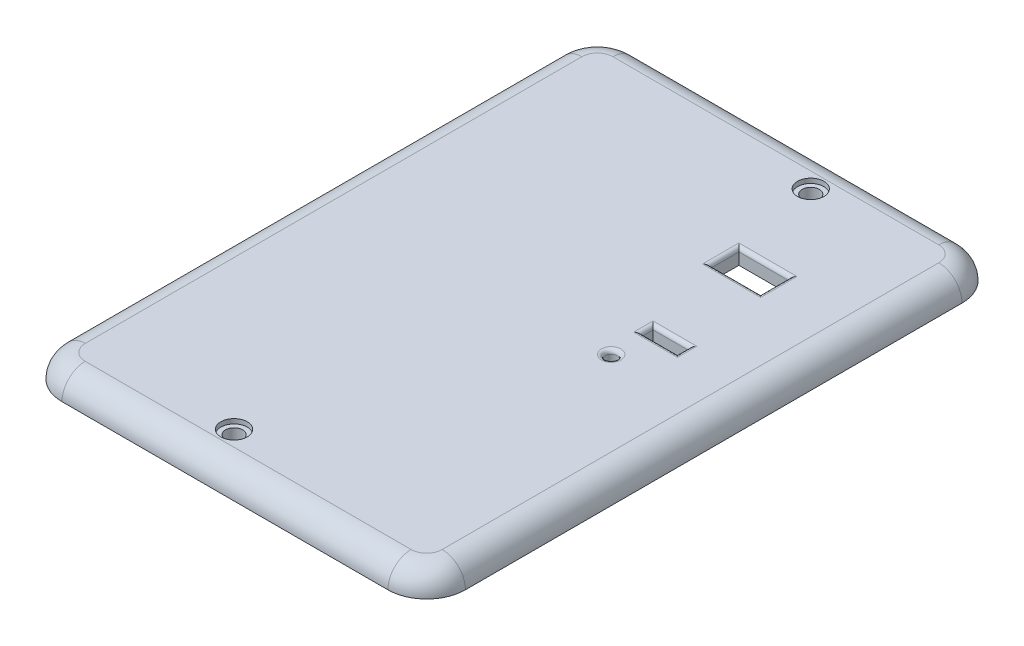
SolidWorks part; units mm, degrees
ref_plane "Front Plane" through (0, 0, 0) normal (0, 0, 1) x (1, 0, 0)
ref_plane "Top Plane" through (0, 0, 0) normal (0, 1, 0) x (1, 0, 0)
ref_plane "Right Plane" through (0, 0, 0) normal (1, 0, 0) x (0, 0, -1)
sketch "Sketch1" plane through (0, 0, 0) normal (0, 1, 0) x (1, 0, 0)
  line L1 (-19.2069, 30.931) -> (22.7931, 30.931)
  line L2 (-24.2069, 25.931) -> (-24.2069, -38.069)
  line L3 (-19.2069, -43.069) -> (22.7931, -43.069)
  line L4 (27.7931, 25.931) -> (27.7931, -38.069)
  arc A0 (22.7931, -43.069) -> (27.7931, -38.069) centre (22.7931, -38.069) ccw
  arc A1 (-24.2069, -38.069) -> (-19.2069, -43.069) centre (-19.2069, -38.069) ccw
  arc A2 (22.7931, 30.931) -> (27.7931, 25.931) centre (22.7931, 25.931) cw
  arc A3 (-19.2069, 30.931) -> (-24.2069, 25.931) centre (-19.2069, 25.931) ccw
  point P6 (27.7931, -43.069)
  point P11 (27.7931, 30.931)
  point P14 (-24.2069, 30.931)
  dimension "D3" = 5
  dimension "D1" = 52
  dimension "D2" = 74
extrude "Boss-Extrude1" add sketch "Sketch1" along normal blind 3
sketch "Sketch3" plane through (0, 0, 0) normal (0, -1, 0) x (-1, 0, 0)
  line L0 (24.2069, 25.931) -> (24.2069, -38.069) construction
  line L1 (18.2069, 29.931) -> (-21.7931, 29.931)
  line L2 (23.2069, 24.931) -> (23.2069, -37.069)
  line L3 (18.2069, -42.069) -> (-21.7931, -42.069)
  line L4 (-26.7931, 24.931) -> (-26.7931, -37.069)
  line L5 (-27.7931, -38.069) -> (-27.7931, 25.931) construction
  line L6 (19.2069, -43.069) -> (-22.7931, -43.069) construction
  line L7 (-22.7931, 30.931) -> (19.2069, 30.931) construction
  arc A0 (-21.7931, 29.931) -> (-26.7931, 24.931) centre (-21.7931, 24.931) ccw
  arc A1 (-21.7931, -42.069) -> (-26.7931, -37.069) centre (-21.7931, -37.069) cw
  arc A2 (23.2069, -37.069) -> (18.2069, -42.069) centre (18.2069, -37.069) cw
  arc A3 (18.2069, 29.931) -> (23.2069, 24.931) centre (18.2069, 24.931) cw
  dimension "D5" = 5
  dimension "D1" = 1
  dimension "D2" = 1
  dimension "D3" = 1
  dimension "D4" = 1
extrude "Cut-Extrude1" cut sketch "Sketch3" against normal blind 1
fillet "Fillet1" radius 3 8 edges at (-22.7424, 3, -29.4666) (1.7931, 3, -30.931) (26.3286, 3, -29.4666) (27.7931, 3, 6.069) (26.3286, 3, 41.6045) (1.7931, 3, 43.069) (-22.7424, 3, 41.6045) (-24.2069, 3, 6.069)
sketch "Sketch6" plane through (0, 1, 0) normal (0, -1, 0) x (1, 0, 0)
  line L0 (-23.2069, 37.069) -> (-23.2069, -24.931) construction
  line L1 (-22.6069, -4.231) -> (-10.6069, -4.231)
  line L2 (-22.6069, -4.231) -> (-22.6069, 16.269)
  line L3 (-22.6069, 16.269) -> (-10.6069, 16.269)
  line L4 (-10.6069, -4.231) -> (-10.6069, 16.269)
  line L5 (22.7931, -30.931) -> (-19.2069, -30.931) construction
  dimension "D1" = 12
  dimension "D2" = 20.5
  dimension "D3" = 0.6
  dimension "D4" = 26.7
extrude "Boss-Extrude3" add sketch "Sketch6" along normal blind 4.5
sketch "Sketch13" plane through (0, -3.5, 0) normal (0, -1, 0) x (1, 0, 0)
  line L0 (-10.6069, 16.269) -> (-22.6069, 16.269) construction
  line L1 (-15.1069, 16.269) -> (-12.1069, 16.269)
  line L2 (-15.1069, 16.269) -> (-15.1069, -4.231)
  line L3 (-15.1069, -4.231) -> (-12.1069, -4.231)
  line L4 (-12.1069, 16.269) -> (-12.1069, -4.231)
  line L5 (-22.6069, -4.231) -> (-10.6069, -4.231) construction
  line L6 (-22.6069, 16.269) -> (-22.6069, -4.231) construction
  dimension "D1" = 7.5
  dimension "D2" = 3
sketch "Sketch28" plane through (0, -3.5, 0) normal (0, -1, 0) x (1, 0, 0)
  line L0 (-22.6069, -4.231) -> (-10.6069, -4.231) construction
  line L1 (-22.6069, 16.269) -> (-22.3069, 16.269)
  line L2 (-22.6069, 16.269) -> (-22.6069, -4.231)
  line L3 (-22.6069, -4.231) -> (-22.3069, -4.231)
  line L4 (-22.3069, 16.269) -> (-22.3069, -4.231)
  dimension "D1" = 0.3
extrude "Cut-Extrude18" cut sketch "Sketch28" against normal blind 4.5
sketch "Sketch44" plane through (0, 1, 0) normal (0, -1, 0) x (1, 0, 0)
  line L0 (21.7931, 42.069) -> (-18.2069, 42.069) construction
  line L2 (26.7931, -24.931) -> (26.7931, 37.069) construction
  circle A0 centre (-2.0269, 38.069) radius 1.1
  dimension "D1" = 4
  dimension "D2" = 28.82
extrude "Cut-Extrude26" cut sketch "Sketch44" against normal blind 10
sketch "Sketch45" plane through (0, 1, 0) normal (0, -1, 0) x (1, 0, 0)
  line L0 (-18.2069, -29.931) -> (21.7931, -29.931) construction
  line L1 (26.7931, -24.931) -> (26.7931, 37.069) construction
  circle A0 centre (8.2931, -25.931) radius 1.1
  dimension "D1" = 4
  dimension "D2" = 18.5
extrude "Cut-Extrude27" cut sketch "Sketch45" against normal blind 10
sketch "Sketch47" plane through (0, 3, 0) normal (0, 1, 0) x (1, 0, 0)
  circle A0 centre (8.2931, 25.931) radius 1.7
  circle A1 centre (-2.0269, -38.069) radius 1.7
extrude "Cut-Extrude29" cut sketch "Sketch47" against normal blind 0.6
extrude "Cut-Extrude30" cut sketch "Sketch13" against normal blind 3 contours L2 L3 L4 L1
sketch "Sketch48" plane through (0, 3, 0) normal (0, 1, 0) x (1, 0, 0)
  line L0 (13.3693, 0.5278) -> (18.0165, -0.9722) construction
  line L1 (13.3693, -0.9722) -> (18.0165, -0.9722)
  line L2 (13.3693, -0.9722) -> (13.3693, 0.5278)
  line L3 (13.3693, 0.5278) -> (18.0165, 0.5278)
  line L4 (18.0165, -0.9722) -> (18.0165, 0.5278)
  line L9 (18.0165, 0.5278) -> (13.3693, -0.9722) construction
  line L10 (13.3693, -0.2222) -> (18.0165, -0.2222) construction
  circle A0 centre (13.9198, -5.4182) radius 0.75
  dimension "D1" = 0.75
sketch "Sketch49" plane through (0, 3, 0) normal (0, 1, 0) x (1, 0, 0)
  line L1 (10.2017, 14.7694) -> (16.6873, 14.7694)
  line L2 (10.2017, 14.7694) -> (10.2017, 11.0747)
  line L3 (10.2017, 11.0747) -> (16.6873, 11.0747)
  line L4 (16.6873, 14.7694) -> (16.6873, 11.0747)
extrude "Cut-Extrude31" cut sketch "Sketch49" against normal blind 8
extrude "Cut-Extrude33" cut sketch "Sketch48" against normal blind 8
fillet "Fillet2" radius 0.5 9 edges at (13.9198, 3, 6.1682) (15.6929, 3, 0.9722) (18.0165, 3, 0.2222) (13.3693, 3, 0.2222) (15.6929, 3, -0.5278) (13.4445, 3, -11.0747) (16.6873, 3, -12.922) (10.2017, 3, -12.922) (13.4445, 3, -14.7694)
sketch "Sketch51" plane through (0, 0, 0) normal (0, 1, 0) x (1, 0, 0)
  line L0 (26.7931, 24.931) -> (26.7931, -37.069) construction
  line L1 (-18.2069, 29.931) -> (21.7931, 29.931) construction
  line L2 (-23.2069, -37.069) -> (-23.2069, 24.931) construction
  line L3 (21.7931, -42.069) -> (-18.2069, -42.069) construction
  line L4 (26.7931, 24.931) -> (26.7931, -37.069)
  line L5 (-18.2069, 29.931) -> (21.7931, 29.931)
  line L6 (-23.2069, -37.069) -> (-23.2069, 24.931)
  line L7 (21.7931, -42.069) -> (-18.2069, -42.069)
  line L8 (21.7931, -41.569) -> (-18.2069, -41.569)
  line L9 (-22.7069, -37.069) -> (-22.7069, 24.931)
  line L10 (-18.2069, 29.431) -> (21.7931, 29.431)
  line L11 (26.2931, 24.931) -> (26.2931, -37.069)
  arc A0 (21.7931, -42.069) -> (26.7931, -37.069) centre (21.7931, -37.069) ccw construction
  arc A1 (26.7931, 24.931) -> (21.7931, 29.931) centre (21.7931, 24.931) ccw construction
  arc A2 (-18.2069, 29.931) -> (-23.2069, 24.931) centre (-18.2069, 24.931) ccw construction
  arc A3 (-23.2069, -37.069) -> (-18.2069, -42.069) centre (-18.2069, -37.069) ccw construction
  arc A4 (21.7931, -42.069) -> (26.7931, -37.069) centre (21.7931, -37.069) ccw
  arc A5 (26.7931, 24.931) -> (21.7931, 29.931) centre (21.7931, 24.931) ccw
  arc A6 (-18.2069, 29.931) -> (-23.2069, 24.931) centre (-18.2069, 24.931) ccw
  arc A7 (-23.2069, -37.069) -> (-18.2069, -42.069) centre (-18.2069, -37.069) ccw
  arc A8 (-22.7069, -37.069) -> (-18.2069, -41.569) centre (-18.2069, -37.069) ccw
  arc A9 (-18.2069, 29.431) -> (-22.7069, 24.931) centre (-18.2069, 24.931) ccw
  arc A10 (26.2931, 24.931) -> (21.7931, 29.431) centre (21.7931, 24.931) ccw
  arc A11 (21.7931, -41.569) -> (26.2931, -37.069) centre (21.7931, -37.069) ccw
  dimension "D1" = 0.5
extrude "Boss-Extrude4" add sketch "Sketch51" along normal up to surface (1 mm away) up to face at (15.6929, 1, 0.2222)
